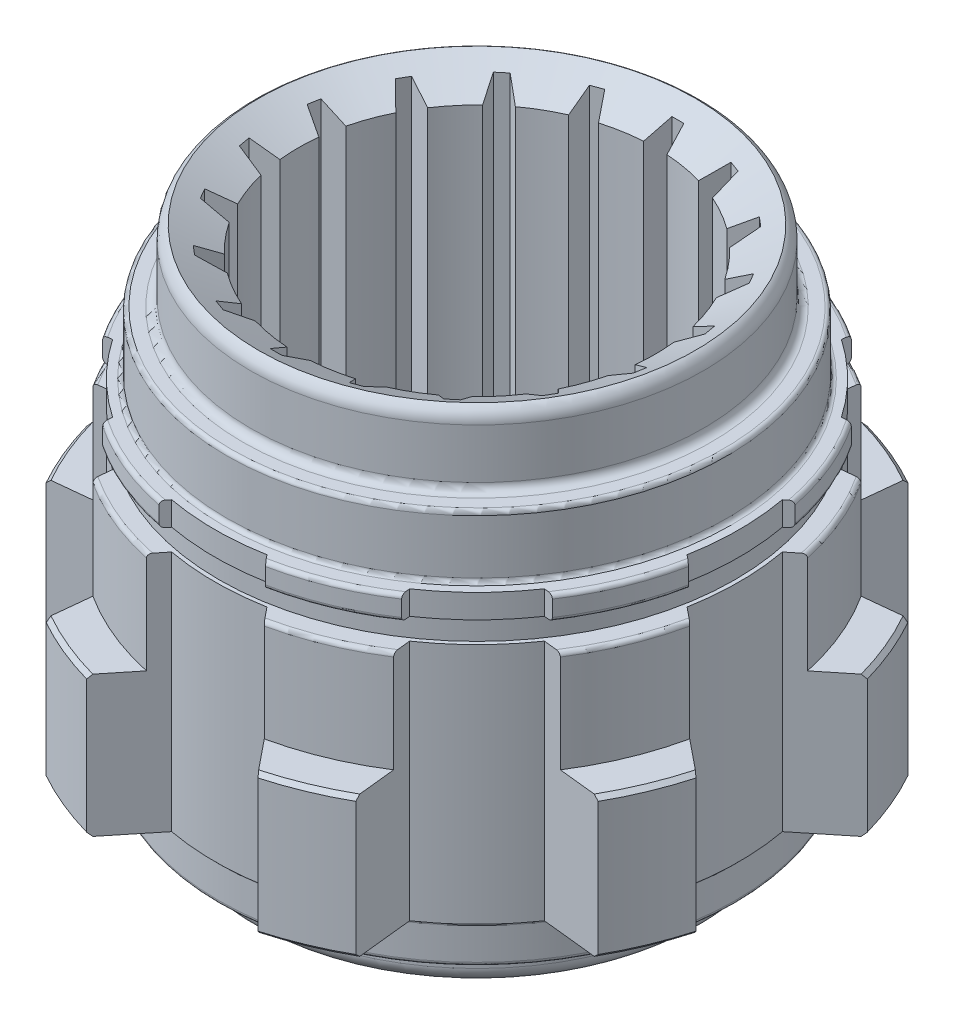
SolidWorks part; units mm, degrees
ref_plane "Plano frontal" through (0, 0, 0) normal (0, 0, 1) x (1, 0, 0)
ref_plane "Plano superior" through (0, 0, 0) normal (0, 1, 0) x (1, 0, 0)
ref_plane "Plano direito" through (0, 0, 0) normal (1, 0, 0) x (0, 0, -1)
sketch "Esboço1" plane through (0, 0, 0) normal (0, 0, 1) x (1, 0, 0)
  line L0 (0, -54.4613) -> (0, 50.8185) construction
  line L1 (22.5, 50.8185) -> (28.5, 50.8185)
  line L2 (28.5, 50.8185) -> (28.5, 41.8185)
  line L3 (28.5, 41.8185) -> (31.5, 41.8185)
  line L4 (31.5, 41.8185) -> (31.5, 34.0185)
  line L5 (31.5, 34.0185) -> (34, 34.0185)
  line L6 (34, 34.0185) -> (34, 31.0185)
  line L7 (34, 31.0185) -> (32.5, 31.0185)
  line L8 (32.5, 31.0185) -> (32.5, 28.3185)
  line L9 (32.5, 28.3185) -> (35, 28.3185)
  line L10 (35, 28.3185) -> (35, 15.5185)
  line L11 (35, 15.5185) -> (39.85, 15.5185)
  line L12 (39.85, 15.5185) -> (39.85, -2.1815)
  line L13 (39.85, -2.1815) -> (32.5, -2.1815)
  line L14 (32.5, -2.1815) -> (32.5, -7.1815)
  line L15 (32.5, -7.1815) -> (28.5, -7.1815)
  line L16 (28.5, -7.1815) -> (28.5, -12.1815)
  line L17 (28.5, -12.1815) -> (22.5, -12.1815)
  line L18 (22.5, -12.1815) -> (22.5, 50.8185)
  dimension "D1" = 22.5
  dimension "D2" = 28.5
  dimension "D3" = 31.5
  dimension "D4" = 34
  dimension "D5" = 32.5
  dimension "D6" = 35
  dimension "D7" = 39.85
  dimension "D8" = 32.5
  dimension "D9" = 28.5
  dimension "D10" = 5
  dimension "D11" = 5
  dimension "D12" = 17.7
  dimension "D13" = 3
  dimension "D14" = 2.7
  dimension "D15" = 18.5
  dimension "D16" = 7.8
  dimension "D17" = 63
revolve "Revolução1" add sketch "Esboço1" angle 360 about L0
chamfer "Chamfer1" distance 5 angle 30 2 edges at (0, -12.1815, -22.5) (0, 50.8185, -22.5)
sketch "Sketch1" plane through (0, 50.8185, 0) normal (0, 1, 0) x (1, 0, 0)
  line L0 (0, 0) -> (-52.3995, 0) construction
  line L1 (0, 0) -> (0, 22.5) construction
  line L2 (-1.5, 22.3214) -> (1.5, 22.3214)
  line L3 (-0.75, 25.3) -> (0.75, 25.3)
  line L4 (6.2248, 21.4883) -> (9.0439, 20.4623)
  line L5 (7.9483, 24.0307) -> (9.3579, 23.5177)
  line L6 (-1.5, 22.3214) -> (-0.75, 25.3)
  line L7 (0.75, 25.3) -> (1.5, 22.3214)
  line L8 (6.2248, 21.4883) -> (7.9483, 24.0307)
  line L9 (9.3579, 23.5177) -> (9.0439, 20.4623)
  line L10 (13.1989, 18.0634) -> (15.497, 16.135)
  line L11 (15.688, 19.863) -> (16.8371, 18.8988)
  line L12 (13.1989, 18.0634) -> (15.688, 19.863)
  line L13 (16.8371, 18.8988) -> (15.497, 16.135)
  line L14 (18.5809, 12.4598) -> (20.0809, 9.8617)
  line L15 (21.5354, 13.2995) -> (22.2854, 12.0005)
  line L16 (18.5809, 12.4598) -> (21.5354, 13.2995)
  line L17 (22.2854, 12.0005) -> (20.0809, 9.8617)
  line L18 (21.7219, 5.3533) -> (22.2428, 2.3989)
  line L19 (24.7854, 5.1319) -> (25.0459, 3.6547)
  line L20 (21.7219, 5.3533) -> (24.7854, 5.1319)
  line L21 (25.0459, 3.6547) -> (22.2428, 2.3989)
  line L22 (22.2428, -2.3989) -> (21.7219, -5.3533)
  line L23 (25.0459, -3.6547) -> (24.7854, -5.1319)
  line L24 (22.2428, -2.3989) -> (25.0459, -3.6547)
  line L25 (24.7854, -5.1319) -> (21.7219, -5.3533)
  line L26 (20.0809, -9.8617) -> (18.5809, -12.4598)
  line L27 (22.2854, -12.0005) -> (21.5354, -13.2995)
  line L28 (20.0809, -9.8617) -> (22.2854, -12.0005)
  line L29 (21.5354, -13.2995) -> (18.5809, -12.4598)
  line L30 (15.497, -16.135) -> (13.1989, -18.0634)
  line L31 (16.8371, -18.8988) -> (15.688, -19.863)
  line L32 (15.497, -16.135) -> (16.8371, -18.8988)
  line L33 (15.688, -19.863) -> (13.1989, -18.0634)
  line L34 (9.0439, -20.4623) -> (6.2248, -21.4883)
  line L35 (9.3579, -23.5177) -> (7.9483, -24.0307)
  line L36 (9.0439, -20.4623) -> (9.3579, -23.5177)
  line L37 (7.9483, -24.0307) -> (6.2248, -21.4883)
  line L38 (1.5, -22.3214) -> (-1.5, -22.3214)
  line L39 (0.75, -25.3) -> (-0.75, -25.3)
  line L40 (1.5, -22.3214) -> (0.75, -25.3)
  line L41 (-0.75, -25.3) -> (-1.5, -22.3214)
  line L42 (-6.2248, -21.4883) -> (-9.0439, -20.4623)
  line L43 (-7.9483, -24.0307) -> (-9.3579, -23.5177)
  line L44 (-6.2248, -21.4883) -> (-7.9483, -24.0307)
  line L45 (-9.3579, -23.5177) -> (-9.0439, -20.4623)
  line L46 (-13.1989, -18.0634) -> (-15.497, -16.135)
  line L47 (-15.688, -19.863) -> (-16.8371, -18.8988)
  line L48 (-13.1989, -18.0634) -> (-15.688, -19.863)
  line L49 (-16.8371, -18.8988) -> (-15.497, -16.135)
  line L50 (-18.5809, -12.4598) -> (-20.0809, -9.8617)
  line L51 (-21.5354, -13.2995) -> (-22.2854, -12.0005)
  line L52 (-18.5809, -12.4598) -> (-21.5354, -13.2995)
  line L53 (-22.2854, -12.0005) -> (-20.0809, -9.8617)
  line L54 (-21.7219, -5.3533) -> (-22.2428, -2.3989)
  line L55 (-24.7854, -5.1319) -> (-25.0459, -3.6547)
  line L56 (-21.7219, -5.3533) -> (-24.7854, -5.1319)
  line L57 (-25.0459, -3.6547) -> (-22.2428, -2.3989)
  line L58 (-22.2428, 2.3989) -> (-21.7219, 5.3533)
  line L59 (-25.0459, 3.6547) -> (-24.7854, 5.1319)
  line L60 (-22.2428, 2.3989) -> (-25.0459, 3.6547)
  line L61 (-24.7854, 5.1319) -> (-21.7219, 5.3533)
  line L62 (-20.0809, 9.8617) -> (-18.5809, 12.4598)
  line L63 (-22.2854, 12.0005) -> (-21.5354, 13.2995)
  line L64 (-20.0809, 9.8617) -> (-22.2854, 12.0005)
  line L65 (-21.5354, 13.2995) -> (-18.5809, 12.4598)
  line L66 (-15.497, 16.135) -> (-13.1989, 18.0634)
  line L67 (-16.8371, 18.8988) -> (-15.688, 19.863)
  line L68 (-15.497, 16.135) -> (-16.8371, 18.8988)
  line L69 (-15.688, 19.863) -> (-13.1989, 18.0634)
  line L70 (-9.0439, 20.4623) -> (-6.2248, 21.4883)
  line L71 (-9.3579, 23.5177) -> (-7.9483, 24.0307)
  line L72 (-9.0439, 20.4623) -> (-9.3579, 23.5177)
  line L73 (-7.9483, 24.0307) -> (-6.2248, 21.4883)
  circle A1 centre (0, 0) radius 22.5 construction
  point P81 (0, 0)
  dimension "D1" = 18
extrude "Cut-Extrude1" cut sketch "Sketch1" against normal blind 80
fillet "Filete1" radius 2 1 edges at (0, 50.8185, -28.5)
fillet "Filete2" radius 1 1 edges at (0, 41.8185, -28.5)
fillet "Filete3" radius 0.5 5 edges at (0, 28.3185, -35) (0, 31.0185, -34) (0, 34.0185, -34) (0, 34.0185, -31.5) (0, 41.8185, -31.5)
chamfer "Chanfro1" distance 0.5 angle 45 2 edges at (0, -2.1815, -39.85) (0, 15.5185, -39.85)
fillet "Filete4" radius 2 1 edges at (0, -12.1815, -28.5)
fillet "Filete5" radius 0.5 3 edges at (0, -2.1815, -32.5) (0, -7.1815, -32.5) (0, -7.1815, -28.5)
sketch "Esboço2" plane through (0, -12.1815, 0) normal (0, -1, 0) x (1, 0, 0)
  line L0 (-6, -32.45) -> (-13.6971, -41.9551)
  line L1 (6, -32.45) -> (13.6971, -41.9551)
  line L2 (0, 0) -> (0, -41.6775) construction
  line L3 (-13.6971, -41.9551) -> (13.6971, -41.9551)
  line L4 (13.6971, -41.9551) -> (14.0281, -41.8701)
  line L5 (-27.1882, -18.7029) -> (-39.3521, -19.9814)
  line L6 (-18.7029, -27.1882) -> (-19.9814, -39.3521)
  line L7 (-39.3521, -19.9814) -> (-19.9814, -39.3521)
  line L8 (-19.9814, -39.3521) -> (-19.6873, -39.526)
  line L9 (-32.45, 6) -> (-41.9551, 13.6971)
  line L10 (-32.45, -6) -> (-41.9551, -13.6971)
  line L11 (-41.9551, 13.6971) -> (-41.9551, -13.6971)
  line L12 (-41.9551, -13.6971) -> (-41.8701, -14.0281)
  line L13 (-18.7029, 27.1882) -> (-19.9814, 39.3521)
  line L14 (-27.1882, 18.7029) -> (-39.3521, 19.9814)
  line L15 (-19.9814, 39.3521) -> (-39.3521, 19.9814)
  line L16 (-39.3521, 19.9814) -> (-39.526, 19.6873)
  line L17 (6, 32.45) -> (13.6971, 41.9551)
  line L18 (-6, 32.45) -> (-13.6971, 41.9551)
  line L19 (13.6971, 41.9551) -> (-13.6971, 41.9551)
  line L20 (-13.6971, 41.9551) -> (-14.0281, 41.8701)
  line L21 (27.1882, 18.7029) -> (39.3521, 19.9814)
  line L22 (18.7029, 27.1882) -> (19.9814, 39.3521)
  line L23 (39.3521, 19.9814) -> (19.9814, 39.3521)
  line L24 (19.9814, 39.3521) -> (19.6873, 39.526)
  line L25 (32.45, -6) -> (41.9551, -13.6971)
  line L26 (32.45, 6) -> (41.9551, 13.6971)
  line L27 (41.9551, -13.6971) -> (41.9551, 13.6971)
  line L28 (41.9551, 13.6971) -> (41.8701, 14.0281)
  line L29 (18.7029, -27.1882) -> (19.9814, -39.3521)
  line L30 (27.1882, -18.7029) -> (39.3521, -19.9814)
  line L31 (19.9814, -39.3521) -> (39.3521, -19.9814)
  line L32 (39.3521, -19.9814) -> (39.526, -19.6873)
  arc A0 (-27.1882, -18.7029) -> (-18.7029, -27.1882) centre (0, 0) ccw
  arc A1 (-6, -32.45) -> (6, -32.45) centre (0, 0) ccw
  arc A2 (-32.45, 6) -> (-32.45, -6) centre (0, 0) ccw
  arc A3 (-18.7029, 27.1882) -> (-27.1882, 18.7029) centre (0, 0) ccw
  arc A4 (6, 32.45) -> (-6, 32.45) centre (0, 0) ccw
  arc A5 (27.1882, 18.7029) -> (18.7029, 27.1882) centre (0, 0) ccw
  arc A6 (32.45, -6) -> (32.45, 6) centre (0, 0) ccw
  arc A7 (18.7029, -27.1882) -> (27.1882, -18.7029) centre (0, 0) ccw
  dimension "D1" = 78
  dimension "D2" = 8
extrude "Corte-extrusão1" cut sketch "Esboço2" against normal through all
